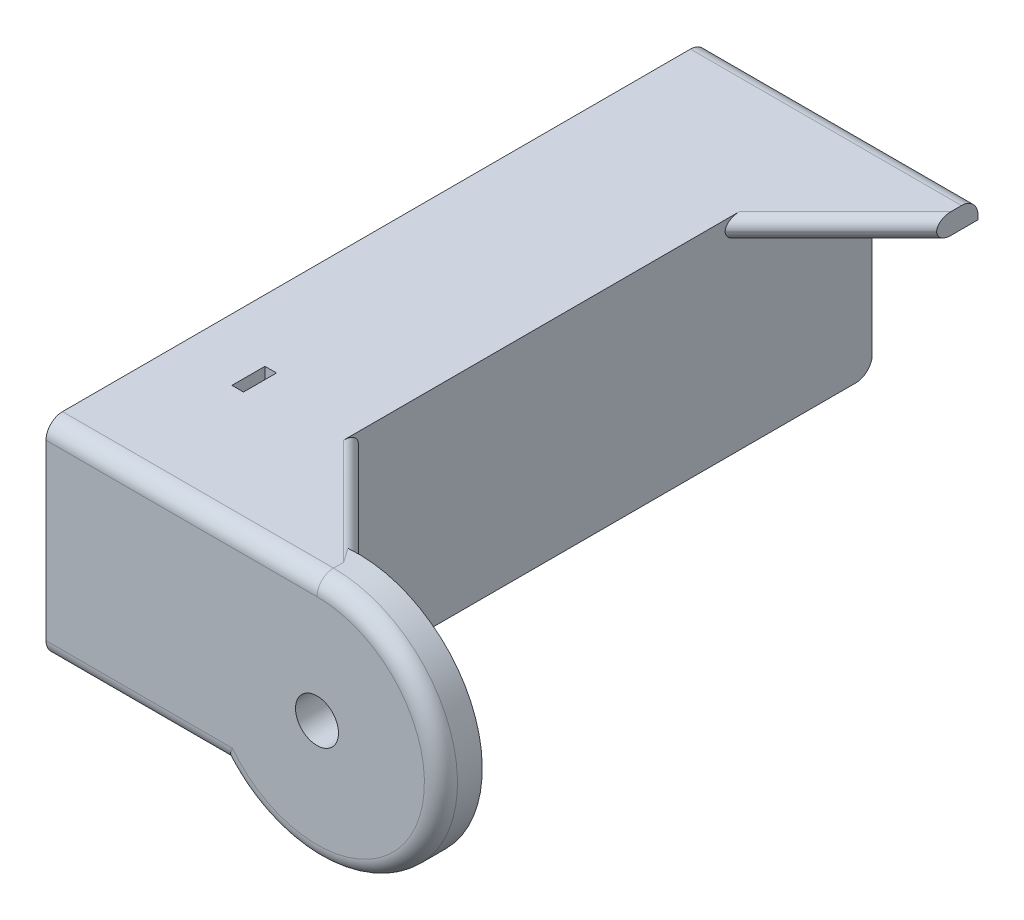
SolidWorks part; units mm, degrees
ref_plane "Front Plane" through (0, 0, 0) normal (0, 0, 1) x (1, 0, 0)
ref_plane "Top Plane" through (0, 0, 0) normal (0, 1, 0) x (1, 0, 0)
ref_plane "Right Plane" through (0, 0, 0) normal (1, 0, 0) x (0, 0, -1)
sketch "Sketch1" plane through (0, 0, 0) normal (0, 1, 0) x (1, 0, 0)
  line L0 (12.7, 50.8) -> (-12.7, -50.8) construction
  line L1 (-12.7, 50.8) -> (12.7, 50.8)
  line L2 (-12.7, 50.8) -> (-12.7, -50.8)
  line L3 (-12.7, -50.8) -> (12.7, -50.8)
  line L4 (12.7, 50.8) -> (12.7, -50.8)
  dimension "D1" = 25.4
  dimension "D2" = 101.6
extrude "Top" add sketch "Sketch1" along normal blind 4.7625
sketch "Sketch2" plane through (0, 4.7625, 0) normal (0, 1, 0) x (1, 0, 0)
  line L1 (-12.7, 50.8) -> (12.7, 50.8)
  line L2 (-12.7, 50.8) -> (-12.7, -50.8)
  line L3 (-12.7, -50.8) -> (12.7, -50.8)
  line L5 (12.7, 50.8) -> (12.7, -50.8)
  line L6 (-7.9375, 44.45) -> (7.9375, 44.45)
  line L7 (-7.9375, 44.45) -> (-7.9375, -44.45)
  line L8 (-7.9375, -44.45) -> (7.9375, -44.45)
  line L9 (7.9375, 44.45) -> (7.9375, -44.45)
  dimension "D1" = 4.7625
  dimension "D2" = 4.7625
  dimension "D3" = 6.35
  dimension "D4" = 6.35
extrude "Walls" add sketch "Sketch2" against normal blind 31.75
sketch "Sketch9" plane through (0, 0, 50.8) normal (0, 0, -1) x (-1, 0, 0)
  line L0 (-28.956, -14.2875) -> (-12.7, -14.2875) construction
  line L2 (12.7, -26.9875) -> (-12.7, -26.9875) construction
  line L3 (-28.956, 4.7625) -> (-12.7, 4.7625)
  line L8 (-12.7, -26.9875) -> (-12.7, 4.7625)
  line L14 (-14.757, -26.9875) -> (-12.7, -26.9875)
  circle A0 centre (-28.956, -14.2875) radius 19.05 construction
  arc A1 (-28.956, 4.7625) -> (-14.757, -26.9875) centre (-28.956, -14.2875) ccw
  circle A2 centre (-28.956, -14.2875) radius 3.302
  dimension "D2" = 19.05
  dimension "D3" = 6.604
  dimension "D1" = 16.256
extrude "Joint Hinge" add sketch "Sketch9" along normal blind 6.35
sketch "Sketch3" plane through (-12.7, 0, 0) normal (-1, 0, 0) x (0, 0, 1)
  line L0 (-50.8, -11.1125) -> (-31.75, -11.1125) construction
  line L1 (-50.8, 4.7625) -> (-50.8, -26.9875) construction
  line L2 (50.8, -11.1125) -> (38.1, -11.1125) construction
  line L3 (50.8, 4.7625) -> (50.8, -26.9875) construction
  line L4 (-31.75, -11.1125) -> (-31.75, -26.9875) construction
  line L9 (-50.8, -26.9875) -> (50.8, -26.9875) construction
  line L11 (-25.6016, -12.7) -> (-23.0616, -12.7)
  line L13 (-25.6016, -9.525) -> (-23.0616, -9.525)
  line L14 (-23.0616, -12.7) -> (-23.0616, -9.525)
  line L15 (-25.6016, -12.7) -> (-23.0616, -9.525) construction
  line L16 (-25.6016, -9.525) -> (-23.0616, -12.7) construction
  circle A0 centre (38.1, -11.1125) radius 3.175
  circle A1 centre (-31.75, -11.1125) radius 6.35 construction
  arc A2 (-25.6016, -9.525) -> (-25.6016, -12.7) centre (-31.75, -11.1125) ccw
  point P13 (-24.3316, -11.1125)
  dimension "D3" = 6.35
  dimension "D4" = 12.7
  dimension "D1" = 19.05
  dimension "D2" = 12.7
  dimension "D5" = 15.875
  dimension "D6" = 3.175
  dimension "D7" = 2.54
extrude "Shaft holes" cut sketch "Sketch3" against normal blind 23.876
sketch "Sketch13" plane through (0, 0, 0) normal (0, -1, 0) x (1, 0, 0)
  line L1 (-3.175, 26.67) -> (-1.397, 26.67)
  line L2 (-3.175, 26.67) -> (-3.175, 31.75)
  line L3 (-3.175, 31.75) -> (-1.397, 31.75)
  line L4 (-1.397, 26.67) -> (-1.397, 31.75)
  line L5 (-12.7, 50.8) -> (12.7, 50.8) construction
  line L6 (-12.7, -50.8) -> (-12.7, 50.8) construction
  dimension "D1" = 1.778
  dimension "D2" = 5.08
  dimension "D3" = 19.05
  dimension "D4" = 9.525
extrude "Wire Loft Mount" cut sketch "Sketch13" against normal blind 12.7
sketch "Sketch15" plane through (0, 4.7625, 0) normal (0, 1, 0) x (1, 0, 0)
  line L0 (12.7, -44.45) -> (28.956, -44.45)
  line L1 (28.956, -44.45) -> (12.7, -28.194)
  line L2 (12.7, -44.45) -> (12.7, 50.8) construction
  line L3 (12.7, -28.194) -> (12.7, -44.45)
  line L4 (12.7, 28.194) -> (28.956, 44.45)
  line L5 (28.956, 44.45) -> (28.956, 50.8)
  line L6 (28.956, 50.8) -> (12.7, 50.8)
  line L7 (12.7, 50.8) -> (12.7, 28.194)
  dimension "D1" = 45
  dimension "D2" = 6.35
  dimension "D3" = 45
extrude "Anti-flex" add sketch "Sketch15" against normal blind 3.175
fillet "Fillet1" radius 2.54 5 edges at (0, -26.9875, -50.8) (1.0285, -26.9875, 50.8) (46.3462, -22.0646, 50.8) (8.128, 4.7625, 50.8) (8.128, 4.7625, -50.8)
fillet "Fillet2" radius 1.5875 4 edges at (20.828, 1.5875, -36.322) (20.828, 4.7625, -36.322) (20.828, 1.5875, 36.322) (20.828, 4.7625, 36.322)
